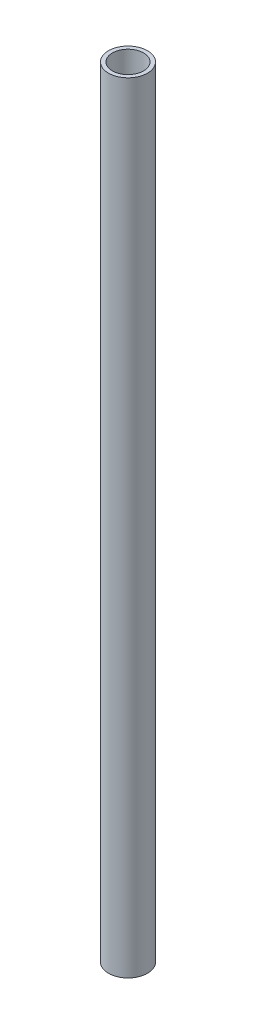
SolidWorks part; units mm, degrees
ref_plane "Front" through (0, 0, 0) normal (0, 0, 1) x (1, 0, 0)
ref_plane "Top" through (0, 0, 0) normal (0, 1, 0) x (1, 0, 0)
ref_plane "Right" through (0, 0, 0) normal (1, 0, 0) x (0, 0, -1)
sketch "Sketch1" plane through (0, 0, 0) normal (0, 1, 0) x (1, 0, 0)
  circle A0 centre (0, 0) radius 5
  dimension "D1" = 10
extrude "Extrude-Thin1" add sketch "Sketch1" along normal blind 200 thin thin type one direction reverse wall 1
